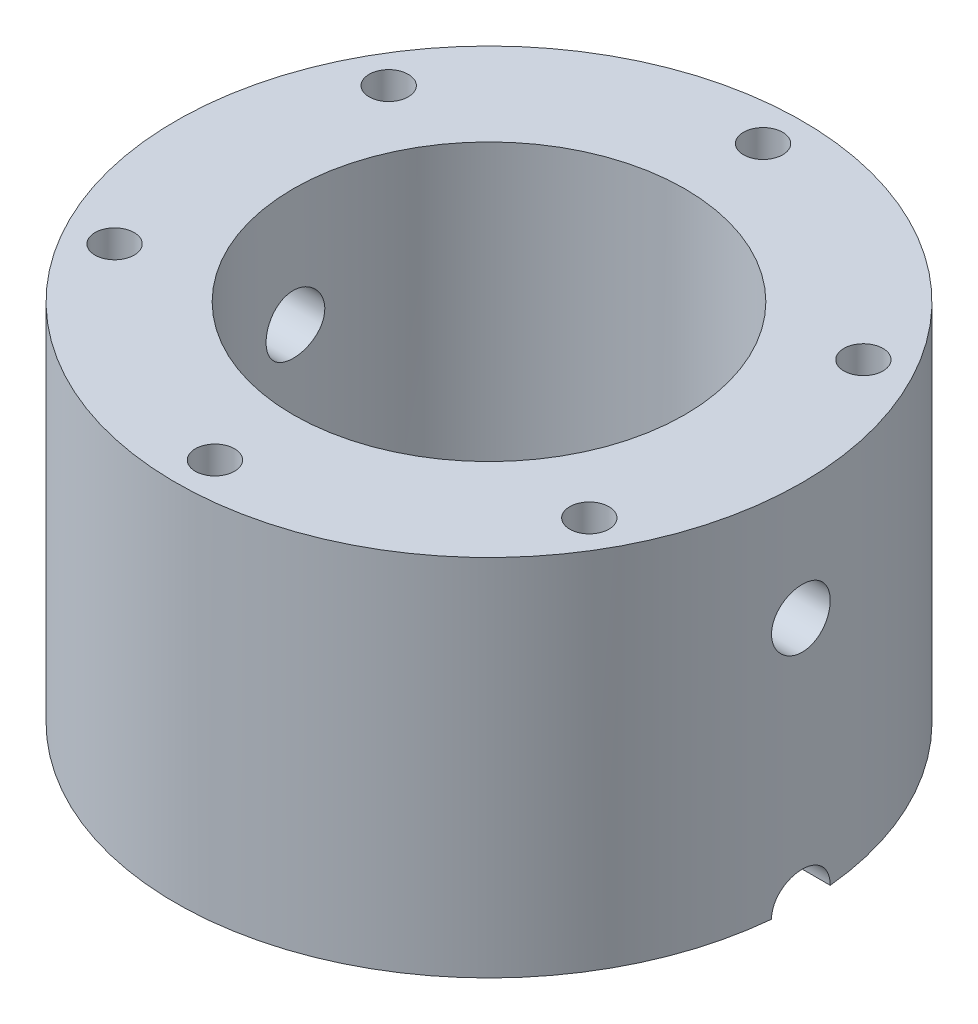
SolidWorks part; units mm, degrees
ref_plane "Front Plane" through (0, 0, 0) normal (0, 0, 1) x (1, 0, 0)
ref_plane "Top Plane" through (0, 0, 0) normal (0, 1, 0) x (1, 0, 0)
ref_plane "Right Plane" through (0, 0, 0) normal (1, 0, 0) x (0, 0, -1)
ref_axis "Centerline" through (0, 13.335, 0) along (0, -1, 0)
sketch "Sketch1" plane through (0, 0, 0) normal (0, 1, 0) x (1, 0, 0)
  circle A0 centre (0, 0) radius 20.32
  dimension "D1" = 40.64
extrude "Cylinder" add sketch "Sketch1" along normal blind 26.162
sketch "Sketch18" plane through (0, 26.162, 0) normal (0, 1, 0) x (1, 0, 0)
  circle A0 centre (0, 0) radius 12.7
  dimension "D1" = 25.4
extrude "Cut-Extrude10" cut sketch "Sketch18" against normal blind 23.368
sketch "Sketch19" plane through (0, 0, 0) normal (0, 0, 1) x (1, 0, 0)
  line L0 (-20.32, 0) -> (20.32, 0) construction
  circle A0 centre (12.573, 0) radius 1.905
  dimension "D2" = 3.81
  dimension "D1" = 12.573
revolve "Cut-Revolve7" cut sketch "Sketch19" angle 360 about axis through (0, 13.335, 0) along (0, -1, 0)
sketch "Sketch21" plane through (0, 26.162, 0) normal (0, 1, 0) x (1, 0, 0)
  line L0 (0, 23.819) -> (0, -25.5254) construction
  circle A0 centre (0, 17.78) radius 1.27
  dimension "D1" = 2.54
  dimension "D2" = 17.78
extrude "Cut-Extrude12" cut sketch "Sketch21" against normal up to next
pattern_circular "CirPattern4" count 6 over 360 about axis through (0, 13.335, 0) along (0, -1, 0) of "Cut-Extrude12"
sketch "Sketch22" plane through (0, 2.794, 0) normal (0, 1, 0) x (1, 0, 0)
  circle A0 centre (0, 0) radius 8.001
  dimension "D1" = 16.002
extrude "Cut-Extrude13" cut sketch "Sketch22" against normal up to next
ref_plane "Inlet Plane" through (20.32, 0, 0) normal (1, 0, 0) x (0, 0, -1)
sketch "Sketch25" plane through (20.32, 0, 0) normal (1, 0, 0) x (0, 0, -1)
  circle A0 centre (0, 0) radius 1.905
  dimension "D1" = 3.81
extrude "Cut-Extrude15" cut sketch "Sketch25" against normal up to next
pattern_circular "CirPattern6" count 2 over 360 about axis through (0, 13.335, 0) along (0, -1, 0) of "Cut-Extrude15"
sketch "Sketch26" plane through (20.32, 0, 0) normal (1, 0, 0) x (0, 0, -1)
  line L0 (0, 26.162) -> (0, -3.7703) construction
  line L1 (20.32, 26.162) -> (-20.32, 26.162) construction
  line L2 (20.32, 26.162) -> (-20.32, 26.162) construction
  circle A0 centre (0, 16.002) radius 1.905
  point P7 (0, 26.1828)
  point P8 (0, 27.0434)
  dimension "D2" = 3.81
  dimension "D1" = 10.16
extrude "Cut-Extrude16" cut sketch "Sketch26" against normal through all
sketch "Sketch27" plane through (0, 0, 0) normal (0, 0, 1) x (1, 0, 0)
  line L0 (-20.32, 26.162) -> (-20.32, 17.907) construction
  line L1 (20.32, 26.162) -> (-20.32, 26.162)
  line L2 (20.32, 26.162) -> (20.32, 23.622)
  line L3 (20.32, 23.622) -> (-20.32, 23.622)
  line L4 (-20.32, 26.162) -> (-20.32, 23.622)
  dimension "D1" = 2.54
extrude "Cut-Extrude17" cut sketch "Sketch27" against normal through all and the other way through all
